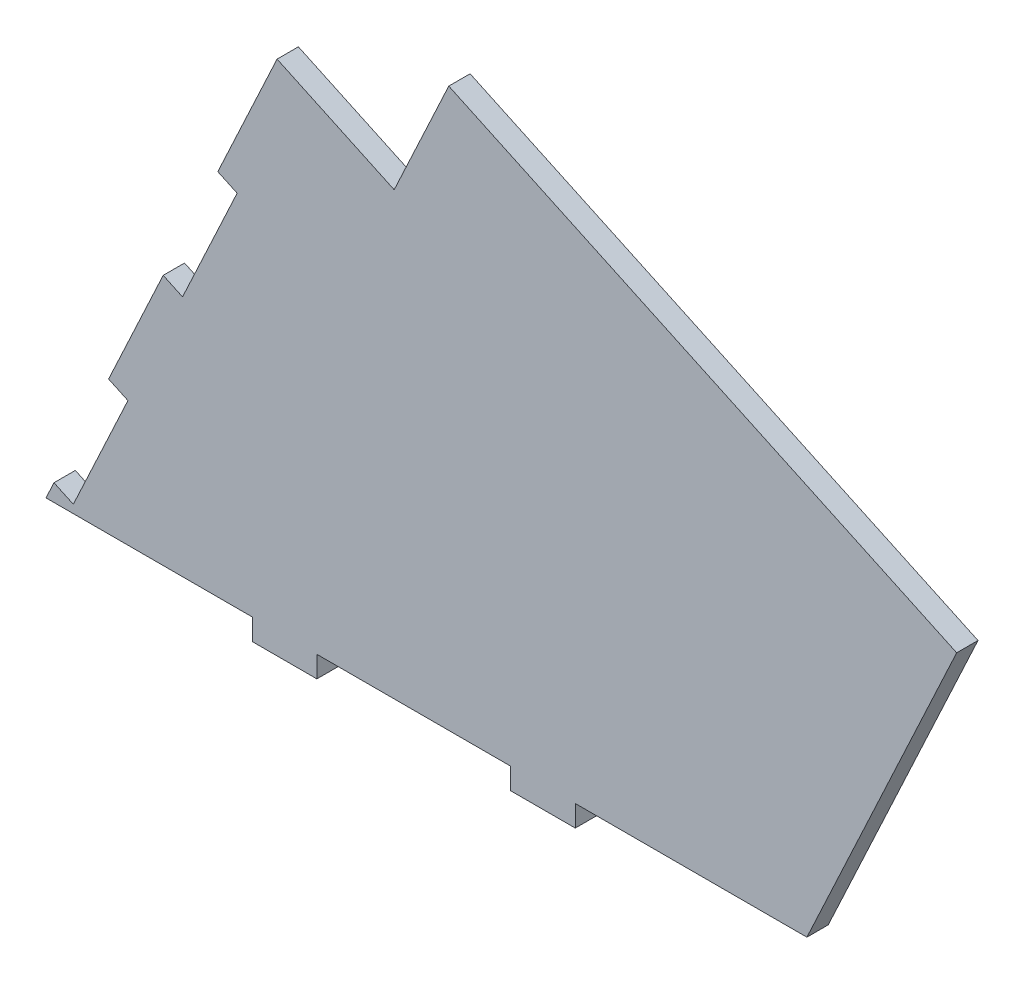
SolidWorks part; units mm, degrees
material "Balsa"
ref_plane "Front Plane" through (0, 0, 0) normal (0, 0, 1) x (1, 0, 0)
ref_plane "Top Plane" through (0, 0, 0) normal (0, 1, 0) x (1, 0, 0)
ref_plane "Right Plane" through (0, 0, 0) normal (1, 0, 0) x (0, 0, -1)
sketch "Sketch1" plane through (0, 0, 396.7) normal (0, 0, 1) x (1, 0, 0)
  line L0 (-321.5462, 12.6346) -> (-203.7639, 12.6346)
  line L2 (-321.5462, 12.6346) -> (-285.7774, 89.341)
  line L3 (-285.7774, 89.341) -> (-267.6513, 80.8887)
  line L4 (-267.6513, 80.8887) -> (-259.1989, 99.0148)
  line L5 (-259.1989, 99.0148) -> (-180.5794, 62.354)
  line L6 (-180.5794, 62.354) -> (-203.7639, 12.6346)
  line L7 (-176.6689, 0) -> (-153.4844, 49.7193) construction
  line L8 (-255.5737, 97.3243) -> (63.4467, -51.4373) construction
  line L10 (-327.4362, 0.0035) -> (-285.7774, 89.341) construction
  line L11 (-285.7774, 89.341) -> (-267.6513, 80.8887) construction
  line L12 (-267.6513, 80.8887) -> (-259.1989, 99.0148) construction
extrude "Boss-Extrude1" add sketch "Sketch1" against normal blind 3.3
sketch "Sketch2" plane through (0, 0, 396.7) normal (0, 0, 1) x (1, 0, 0)
  line L0 (-311.8564, 33.4145) -> (-320.3088, 15.2883)
  line L1 (-311.8564, 33.4145) -> (-308.8656, 32.0199)
  line L2 (-320.3088, 15.2883) -> (-317.3179, 13.8937)
  line L3 (-308.8656, 32.0199) -> (-317.3179, 13.8937)
  line L4 (-303.404, 51.5407) -> (-294.9517, 69.6668)
  line L5 (-303.404, 51.5407) -> (-300.4132, 50.146)
  line L6 (-294.9517, 69.6668) -> (-291.9609, 68.2722)
  line L7 (-300.4132, 50.146) -> (-291.9609, 68.2722)
  line L8 (-300.4132, 50.146) -> (-291.9609, 68.2722) construction
  line L9 (-303.404, 51.5407) -> (-294.9517, 69.6668) construction
extrude "Cut-Extrude1" cut sketch "Sketch2" against normal blind 3.3
sketch "Sketch3" plane through (0, 0, 396.7) normal (0, 0, 1) x (1, 0, 0)
  line L0 (-239.6178, 9.3346) -> (-249.6178, 9.3346)
  line L1 (-239.6178, 9.3346) -> (-239.6178, 12.6346)
  line L2 (-249.6178, 9.3346) -> (-249.6178, 12.6346)
  line L3 (-239.6178, 12.6346) -> (-249.6178, 12.6346)
  line L4 (-279.6178, 9.3346) -> (-289.6178, 9.3346)
  line L5 (-279.6178, 9.3346) -> (-279.6178, 12.6346)
  line L6 (-289.6178, 9.3346) -> (-289.6178, 12.6346)
  line L7 (-279.6178, 12.6346) -> (-289.6178, 12.6346)
  line L8 (-321.5462, 12.6346) -> (-203.7639, 12.6346) construction
extrude "Boss-Extrude2" add sketch "Sketch3" against normal blind 3.3
